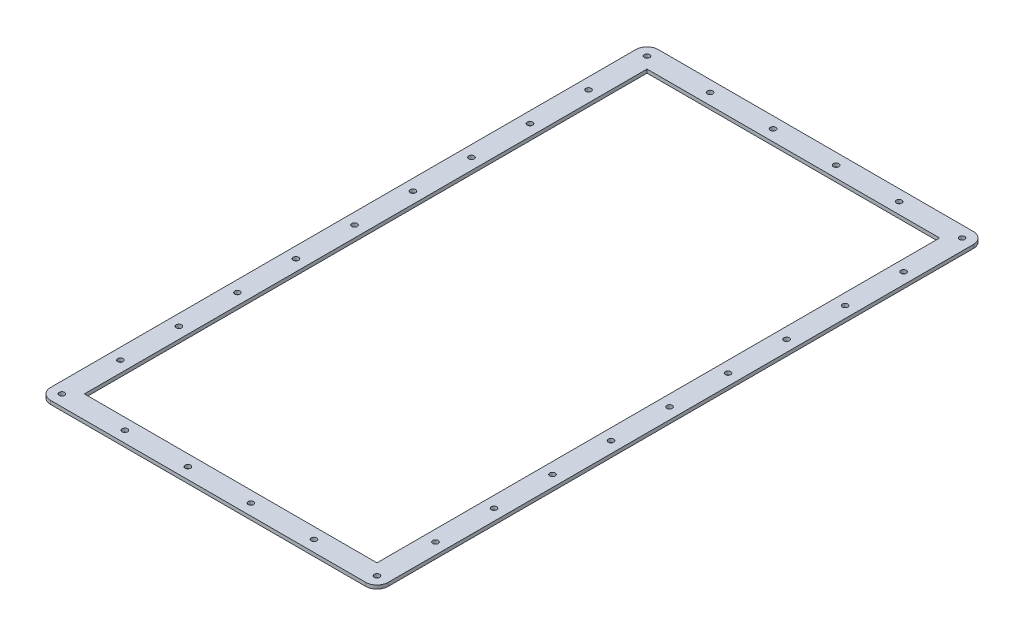
SolidWorks part; units mm, degrees
ref_plane "Front Plane" through (0, 0, 0) normal (0, 0, 1) x (1, 0, 0)
ref_plane "Top Plane" through (0, 0, 0) normal (0, 1, 0) x (1, 0, 0)
ref_plane "Right Plane" through (0, 0, 0) normal (1, 0, 0) x (0, 0, -1)
sketch "Sketch1" plane through (0, 0, 0) normal (0, 1, 0) x (1, 0, 0)
  line L0 (-150, 270) -> (150, 270)
  line L1 (-130, -250) -> (130, -250)
  line L2 (-130, -250) -> (-130, 250)
  line L3 (-130, 250) -> (130, 250)
  line L4 (130, -250) -> (130, 250)
  line L5 (-130, -250) -> (130, 250) construction
  line L6 (-130, 250) -> (130, -250) construction
  line L7 (150, -270) -> (150, 270)
  line L8 (-150, -270) -> (150, -270)
  line L9 (-150, -270) -> (-150, 270)
  line L10 (140, 260) -> (140, 208) construction
  line L11 (0, -270) -> (0, 250) construction
  line L12 (130, 0) -> (-130, 0) construction
  circle A0 centre (140, 260) radius 2.4086
  circle A1 centre (140, 208) radius 2.4086
  circle A2 centre (140, 156) radius 2.4086
  circle A3 centre (140, 104) radius 2.4086
  circle A4 centre (140, 52) radius 2.4086
  circle A5 centre (140, 0) radius 2.4086
  circle A6 centre (140, -52) radius 2.4086
  circle A7 centre (140, -104) radius 2.4086
  circle A8 centre (140, -156) radius 2.4086
  circle A9 centre (140, -208) radius 2.4086
  circle A10 centre (140, -260) radius 2.4086
  circle A11 centre (-140, -260) radius 2.4086
  circle A12 centre (-140, -208) radius 2.4086
  circle A13 centre (-140, -156) radius 2.4086
  circle A14 centre (-140, -104) radius 2.4086
  circle A15 centre (-140, -52) radius 2.4086
  circle A16 centre (-140, 0) radius 2.4086
  circle A17 centre (-140, 52) radius 2.4086
  circle A18 centre (-140, 104) radius 2.4086
  circle A19 centre (-140, 156) radius 2.4086
  circle A20 centre (-140, 208) radius 2.4086
  circle A21 centre (-140, 260) radius 2.4086
  circle A22 centre (84, 260) radius 2.4086
  circle A23 centre (28, 260) radius 2.4086
  circle A24 centre (-28, 260) radius 2.4086
  circle A25 centre (-84, 260) radius 2.4086
  circle A26 centre (-28, -260) radius 2.4086
  circle A27 centre (-84, -260) radius 2.4086
  circle A28 centre (28, -260) radius 2.4086
  circle A29 centre (84, -260) radius 2.4086
  circle A30 centre (84, -260) radius 2.4086
  circle A31 centre (28, -260) radius 2.4086
  circle A32 centre (-28, -260) radius 2.4086
  circle A33 centre (-84, -260) radius 2.4086
  point P0 (0, 0)
  dimension "D2" = 500
  dimension "D3" = 260
  dimension "D5" = 10
  dimension "D4" = 10
  dimension "D7" = 52
  dimension "D1" = 20
  dimension "D6" = 11
  dimension "D8" = 5
extrude "Boss-Extrude1" add sketch "Sketch1" along normal blind 3.175 contours L9 L8 L7 L0 A28 A26 A25 A24 A23 A22 A20 A18 A16 A14 A12 L4 L1 L2 L3 A0 A1 A2 A3 A4 A5 A6 A7 A8 A9 region at (0, 0, -263.8226)
fillet "Fillet1" radius 10 4 edges at (150, 1.5875, 270) (-150, 1.5875, 270) (150, 1.5875, -270) (-150, 1.5875, -270)
equation "\"L\"= 500"
equation "\"W\"= 260"
equation "\"H\"= 110"
equation "\"Compartment Width\"= 100"
equation "\"T\"= 4.7625 * 2 / 3"
equation "\"Inside Fillet Radius\"= 10"
equation "\"Hole\"=15"
equation "\"D2@Sketch1\"=\"L\""
equation "\"D3@Sketch1\"=\"W\""
equation "\"D1@Boss-Extrude1\"=\"T\""
